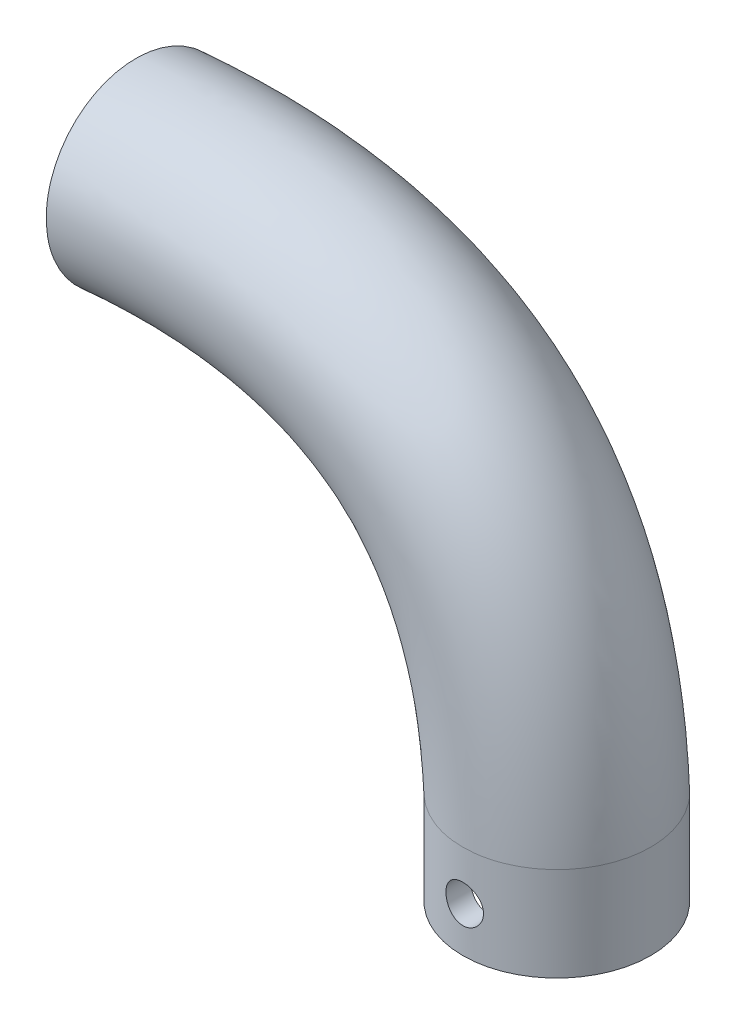
SolidWorks part; units mm, degrees
ref_plane "Front Plane" through (0, 0, 0) normal (0, 0, 1) x (1, 0, 0)
ref_plane "Top Plane" through (0, 0, 0) normal (0, 1, 0) x (1, 0, 0)
ref_plane "Right Plane" through (0, 0, 0) normal (1, 0, 0) x (0, 0, -1)
sketch "Sketch2" plane through (0, 0, 0) normal (0, 0, 1) x (1, 0, 0)
  spline S0 degree 2 poles (0, 0) (-1.8029, 39.292) (-44.3308, 35.3269) knots 0 0 0 1 1 1
sketch "Sketch4" plane through (0, 0, 0) normal (0, 1, 0) x (1, 0, 0)
  circle A0 centre (0, 0) radius 10
  dimension "D1" = 20
sweep "Sweep1" add profiles "Sketch4" path "Sketch2"
sketch "Sketch5" plane through (0, 0, 0) normal (0, -1, 0) x (1, 0, 0)
  circle A0 centre (0, 0) radius 10
  dimension "D1" = 20
extrude "Extrude-Thin1" add sketch "Sketch5" along normal blind 10 thin thin type one direction reverse wall 2.5
ref_plane "Plane2" through (0, 0, 10) normal (0, 0, 1) x (1, 0, 0)
sketch "Sketch7" plane through (0, 0, 10) normal (0, 0, 1) x (1, 0, 0)
  circle A0 centre (0, -5.2289) radius 2
  dimension "D1" = 4
extrude "Cut-Extrude1" cut sketch "Sketch7" against normal through all
